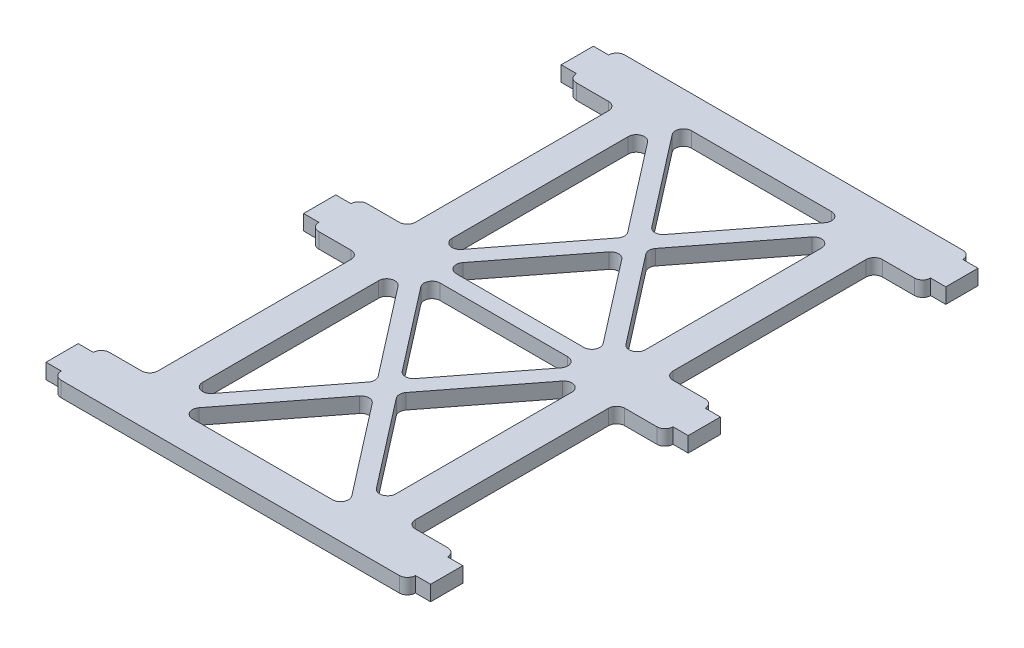
SolidWorks part; units mm, degrees
ref_plane "Front Plane" through (0, 0, 0) normal (0, 0, 1) x (1, 0, 0)
ref_plane "Top Plane" through (0, 0, 0) normal (0, 1, 0) x (1, 0, 0)
ref_plane "Right Plane" through (0, 0, 0) normal (1, 0, 0) x (0, 0, -1)
sketch "Sketch1" plane through (0, 34.29, 0) normal (0, 1, 0) x (1, 0, 0)
  line L0 (28.7528, 190.5) -> (31.75, 190.5) construction
  line L1 (0, -190.5) -> (0, 187.198) construction
  line L2 (38.1028, 187.198) -> (35.1028, 187.198) construction
  line L3 (35.1028, -190.5) -> (38.1, -190.5) construction
  line L5 (-25.4, 65.0875) -> (25.4, 65.0875)
  line L6 (-25.4, 65.0875) -> (-25.4, 176.2125)
  line L7 (-25.4, 176.2125) -> (25.4, 176.2125)
  line L8 (25.4, 65.0875) -> (25.4, 176.2125)
  line L9 (-25.4, 65.0875) -> (25.4, 176.2125) construction
  line L10 (-25.4, 176.2125) -> (25.4, 65.0875) construction
  point P0 (0, 120.65)
  dimension "D1" = 111.125
  dimension "D2" = 50.8
  dimension "D3" = 14.2875
extrude "Boss-Extrude1" add sketch "Sketch1" along normal mid plane 3 contours L7 L8 L5 L6
sketch "Sketch2" plane through (0, 35.79, 0) normal (0, 1, 0) x (1, 0, 0)
  line L0 (0, 176.2125) -> (0, 65.0186) construction
  line L1 (-25.4, 176.2125) -> (25.4, 176.2125) construction
  line L2 (25.4, 120.65) -> (-25.4, 120.65) construction
  line L3 (25.4, 65.0875) -> (25.4, 176.2125) construction
  line L4 (-25.4, 65.0875) -> (-25.4, 176.2125) construction
  line L5 (-34.925, 176.2125) -> (-25.4, 166.6875) construction
  line L6 (34.925, 166.6875) -> (25.4, 166.6875)
  line L7 (34.925, 166.6875) -> (34.925, 176.2125)
  line L8 (34.925, 176.2125) -> (25.4, 176.2125)
  line L9 (25.4, 166.6875) -> (25.4, 176.2125)
  line L10 (34.925, 166.6875) -> (25.4, 176.2125) construction
  line L11 (34.925, 176.2125) -> (25.4, 166.6875) construction
  line L12 (-34.925, 166.6875) -> (-25.4, 176.2125) construction
  line L13 (-25.4, 166.6875) -> (-25.4, 176.2125)
  line L14 (-34.925, 176.2125) -> (-25.4, 176.2125)
  line L15 (-34.925, 166.6875) -> (-34.925, 176.2125)
  line L16 (-34.925, 166.6875) -> (-25.4, 166.6875)
  line L17 (34.925, 115.8875) -> (25.4, 115.8875)
  line L18 (34.925, 115.8875) -> (34.925, 125.4125)
  line L19 (34.925, 125.4125) -> (25.4, 125.4125)
  line L20 (25.4, 115.8875) -> (25.4, 125.4125)
  line L21 (34.925, 115.8875) -> (25.4, 125.4125) construction
  line L22 (34.925, 125.4125) -> (25.4, 115.8875) construction
  line L23 (-25.4, 115.8875) -> (-25.4, 125.4125)
  line L24 (-34.925, 125.4125) -> (-25.4, 125.4125)
  line L25 (-34.925, 115.8875) -> (-34.925, 125.4125)
  line L26 (-34.925, 115.8875) -> (-25.4, 115.8875)
  line L27 (-34.925, 125.4125) -> (-25.4, 115.8875) construction
  line L28 (-34.925, 115.8875) -> (-25.4, 125.4125) construction
  line L29 (34.925, 65.0875) -> (25.4, 65.0875)
  line L30 (34.925, 65.0875) -> (34.925, 74.6125)
  line L31 (34.925, 74.6125) -> (25.4, 74.6125)
  line L32 (25.4, 65.0875) -> (25.4, 74.6125)
  line L33 (34.925, 65.0875) -> (25.4, 74.6125) construction
  line L34 (34.925, 74.6125) -> (25.4, 65.0875) construction
  line L35 (-25.4, 65.0875) -> (-25.4, 74.6125)
  line L36 (-34.925, 74.6125) -> (-25.4, 74.6125)
  line L37 (-34.925, 65.0875) -> (-34.925, 74.6125)
  line L38 (-34.925, 65.0875) -> (-25.4, 65.0875)
  line L39 (-34.925, 74.6125) -> (-25.4, 65.0875) construction
  line L40 (-34.925, 65.0875) -> (-25.4, 74.6125) construction
  point P11 (30.1625, 171.45)
  point P21 (-30.1625, 171.45)
  point P24 (30.1625, 120.65)
  point P33 (-30.1625, 120.65)
  point P34 (30.1625, 69.85)
  point P43 (-30.1625, 69.85)
  dimension "D1" = 9.525
  dimension "D2" = 9.525
  dimension "D3" = 3
extrude "Boss-Extrude2" add sketch "Sketch2" against normal up to surface (3 mm away) up to face at (0, 32.79, -120.65)
sketch "Sketch4" plane through (0, 35.79, 0) normal (0, 1, 0) x (1, 0, 0)
  line L0 (25.4, 125.4125) -> (25.4, 166.6875) construction
  line L1 (-19.05, 169.8625) -> (19.05, 169.8625)
  line L2 (-19.05, 169.8625) -> (-19.05, 71.4375)
  line L3 (-19.05, 71.4375) -> (19.05, 71.4375)
  line L4 (19.05, 169.8625) -> (19.05, 71.4375)
  line L5 (-19.05, 169.8625) -> (19.05, 71.4375) construction
  line L6 (-19.05, 71.4375) -> (19.05, 169.8625) construction
  line L7 (-25.4, 125.4125) -> (-25.4, 166.6875) construction
  line L8 (-34.925, 176.2125) -> (34.925, 176.2125) construction
  line L9 (-34.925, 65.0875) -> (34.925, 65.0875) construction
  line L10 (-19.05, 120.65) -> (19.05, 120.65) construction
  line L11 (19.05, 120.65) -> (-19.05, 169.8625) construction
  line L12 (19.05, 120.65) -> (-19.05, 71.4375) construction
  line L13 (-19.05, 120.65) -> (19.05, 169.8625) construction
  line L14 (19.05, 71.4375) -> (-19.05, 120.65) construction
  line L15 (-19.05, 119.0625) -> (19.05, 119.0625)
  line L16 (-19.05, 122.2375) -> (19.05, 122.2375)
  line L17 (20.3053, 72.4093) -> (-17.0423, 120.65)
  line L18 (-17.0423, 120.65) -> (20.3053, 168.8907)
  line L19 (21.0577, 120.65) -> (-17.7947, 70.4657)
  line L20 (21.0577, 120.65) -> (-17.7947, 170.8343)
  line L21 (17.7947, 70.4657) -> (-21.0577, 120.65)
  line L22 (-21.0577, 120.65) -> (17.7947, 170.8343)
  line L23 (17.0423, 120.65) -> (-20.3053, 72.4093)
  line L24 (17.0423, 120.65) -> (-20.3053, 168.8907)
  point P0 (0, 120.65)
  dimension "D1" = 6.35
  dimension "D2" = 6.35
  dimension "D3" = 6.35
  dimension "D4" = 6.35
  dimension "D5" = 1.5875
  dimension "D6" = 1.5875
  dimension "D7" = 1.5875
  dimension "D8" = 1.5875
extrude "Cut-Extrude1" cut sketch "Sketch4" against normal blind 3 contours L15 L19 L17 L4 | L3 L21 L19 | L23 L21 L15 L2 | L23 L15 L17 | L16 L24 L18 | L20 L16 L4 L18 | L20 L22 L1 | L22 L24 L2 L16 region at (0, 35.79, -162.5248) region at (-13.3692, 35.79, -145.2563) region at (13.3692, 35.79, -145.2563) region at (0, 35.79, -129.046) region at (-13.3692, 35.79, -96.0438) region at (0, 35.79, -112.254) region at (13.3692, 35.79, -96.0438) region at (0, 35.79, -78.7752)
fillet "Fillet1" radius 1.5875 44 edges at (-15.8133, 34.29, -119.0625) (15.8133, 34.29, -119.0625) (0, 34.29, -98.637) (-19.05, 34.29, -118.0568) (-2.0077, 34.29, -96.0438) (-19.05, 34.29, -74.0307) (19.05, 34.29, -167.2693) (19.05, 34.29, -123.2432) (2.0077, 34.29, -145.2563) (17.0423, 34.29, -169.8625) (0, 34.29, -147.8495) (-17.0423, 34.29, -169.8625) (2.0077, 34.29, -96.0438) (19.05, 34.29, -118.0568) (19.05, 34.29, -74.0307) (34.925, 34.29, -65.0875) (34.925, 34.29, -74.6125) (25.4, 34.29, -74.6125) (25.4, 34.29, -115.8875) (34.925, 34.29, -115.8875) (34.925, 34.29, -125.4125) (25.4, 34.29, -125.4125) (25.4, 34.29, -166.6875) (34.925, 34.29, -166.6875) (34.925, 34.29, -176.2125) (-34.925, 34.29, -166.6875) (-25.4, 34.29, -166.6875) (-25.4, 34.29, -125.4125) (-34.925, 34.29, -125.4125) (-34.925, 34.29, -115.8875) (-25.4, 34.29, -115.8875) (-25.4, 34.29, -74.6125) (-34.925, 34.29, -74.6125) (-34.925, 34.29, -65.0875) (-19.05, 34.29, -123.2432) (-19.05, 34.29, -167.2693) (-2.0077, 34.29, -145.2563) (-17.0423, 34.29, -71.4375) (0, 34.29, -93.4505) (17.0423, 34.29, -71.4375) (-15.8133, 34.29, -122.2375) (0, 34.29, -142.663) (15.8133, 34.29, -122.2375) (-34.925, 34.29, -176.2125)
sketch "Sketch5" plane through (0, 35.79, 0) normal (0, 1, 0) x (1, 0, 0)
  line L0 (34.925, 168.275) -> (34.925, 174.625) construction
  line L1 (37.925, 168.275) -> (34.925, 168.275)
  line L2 (37.925, 168.275) -> (37.925, 174.625)
  line L3 (37.925, 174.625) -> (34.925, 174.625)
  line L4 (34.925, 168.275) -> (34.925, 174.625)
  line L5 (37.925, 168.275) -> (34.925, 174.625) construction
  line L6 (37.925, 174.625) -> (34.925, 168.275) construction
  line L7 (34.925, 168.275) -> (34.925, 174.625) construction
  line L8 (34.925, 171.45) -> (36.425, 171.45) construction
  line L9 (0, 196.0278) -> (0, 0) construction
  line L10 (-34.925, 171.45) -> (-36.425, 171.45) construction
  line L11 (-37.925, 174.625) -> (-34.925, 168.275) construction
  line L12 (-37.925, 168.275) -> (-34.925, 174.625) construction
  line L13 (-34.925, 168.275) -> (-34.925, 174.625)
  line L14 (-37.925, 174.625) -> (-34.925, 174.625)
  line L15 (-37.925, 168.275) -> (-37.925, 174.625)
  line L16 (-37.925, 168.275) -> (-34.925, 168.275)
  line L17 (37.925, 117.475) -> (34.925, 117.475)
  line L18 (37.925, 117.475) -> (37.925, 123.825)
  line L19 (37.925, 123.825) -> (34.925, 123.825)
  line L20 (34.925, 117.475) -> (34.925, 123.825)
  line L21 (37.925, 117.475) -> (34.925, 123.825) construction
  line L22 (37.925, 123.825) -> (34.925, 117.475) construction
  line L23 (34.925, 120.65) -> (36.425, 120.65) construction
  line L24 (-34.925, 117.475) -> (-34.925, 123.825)
  line L25 (-37.925, 123.825) -> (-34.925, 123.825)
  line L26 (-37.925, 117.475) -> (-37.925, 123.825)
  line L27 (-37.925, 117.475) -> (-34.925, 117.475)
  line L28 (-34.925, 120.65) -> (-36.425, 120.65) construction
  line L29 (-37.925, 123.825) -> (-34.925, 117.475) construction
  line L30 (-37.925, 117.475) -> (-34.925, 123.825) construction
  line L31 (37.925, 66.675) -> (34.925, 66.675)
  line L32 (37.925, 66.675) -> (37.925, 73.025)
  line L33 (37.925, 73.025) -> (34.925, 73.025)
  line L34 (34.925, 66.675) -> (34.925, 73.025)
  line L35 (37.925, 66.675) -> (34.925, 73.025) construction
  line L36 (37.925, 73.025) -> (34.925, 66.675) construction
  line L37 (34.925, 69.85) -> (36.425, 69.85) construction
  line L38 (-34.925, 66.675) -> (-34.925, 73.025)
  line L39 (-37.925, 73.025) -> (-34.925, 73.025)
  line L40 (-37.925, 66.675) -> (-37.925, 73.025)
  line L41 (-37.925, 66.675) -> (-34.925, 66.675)
  line L42 (-34.925, 69.85) -> (-36.425, 69.85) construction
  line L43 (-37.925, 73.025) -> (-34.925, 66.675) construction
  line L44 (-37.925, 66.675) -> (-34.925, 73.025) construction
  line L45 (-36.425, 171.45) -> (-36.425, 120.65) construction
  point P0 (36.425, 171.45)
  point P7 (36.425, 120.65)
  point P21 (-36.425, 171.45)
  point P35 (-36.425, 120.65)
  point P36 (36.425, 69.85)
  point P49 (-36.425, 69.85)
  dimension "D1" = 3
  dimension "D2" = 6.35
  dimension "D4" = 50.8
  dimension "D3" = 3
extrude "Boss-Extrude3" add sketch "Sketch5" against normal up to surface (3 mm away) up to face at (0, 32.79, -129.3309)
